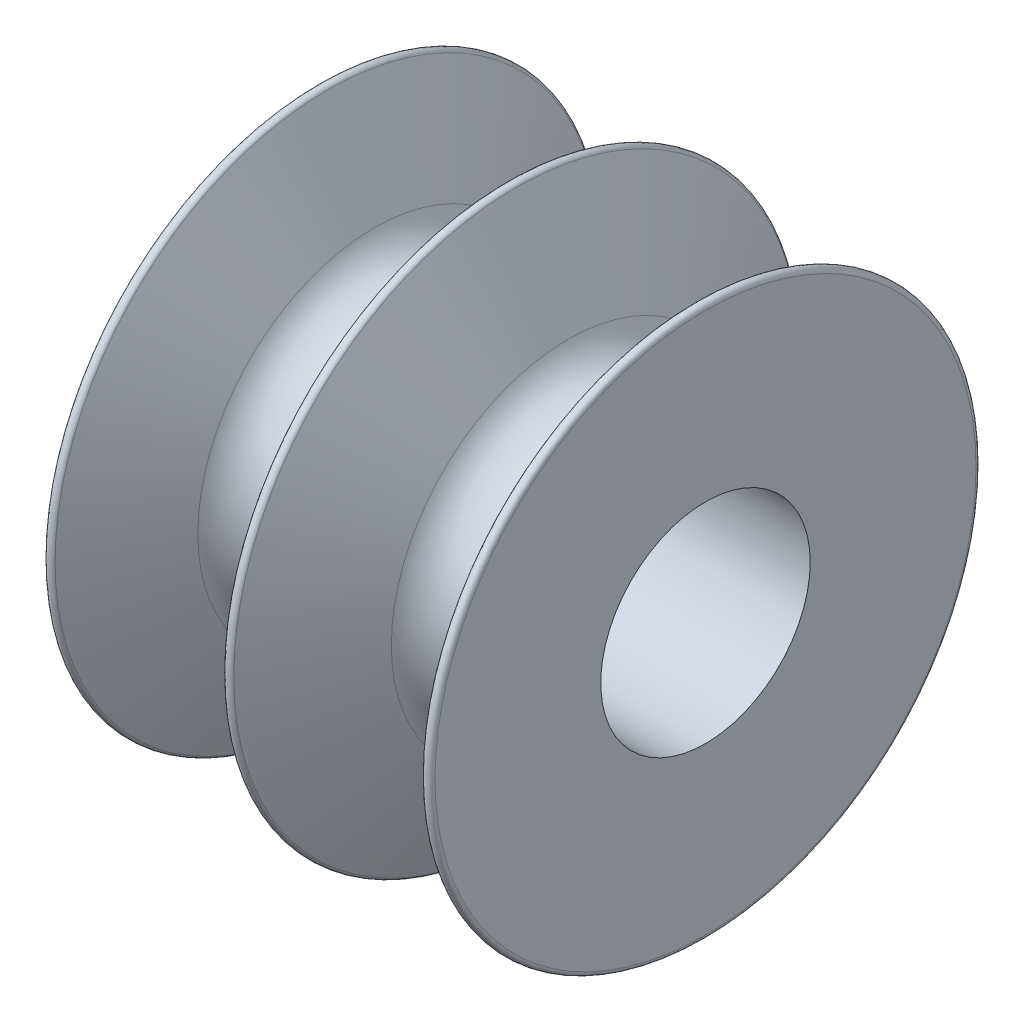
SolidWorks part; units mm, degrees
material "6061-T6 (SS)"
ref_plane "Front Plane" through (0, 0, 0) normal (0, 0, 1) x (1, 0, 0)
ref_plane "Top Plane" through (0, 0, 0) normal (0, 1, 0) x (1, 0, 0)
ref_plane "Right Plane" through (0, 0, 0) normal (1, 0, 0) x (0, 0, -1)
sketch "Sketch1" plane through (0, 0, 0) normal (0, 0, 1) x (1, 0, 0)
  line L0 (-602.9216, 0) -> (29543.159, 0) construction
  line L1 (-601.7144, 8.89) -> (29544.3662, 8.89) construction
  line L2 (0, 8.89) -> (0, -0.2516) construction
  line L3 (-1.905, 0) -> (-1.905, 6.35)
  line L7 (1.905, 0) -> (-1.905, 0)
  line L9 (1.905, 0) -> (1.905, 6.35)
  line L10 (-1.905, 6.35) -> (-1.0702, 4.6376)
  line L11 (1.905, 6.35) -> (1.0702, 4.6376)
  line L12 (1.905, 6.35) -> (2.54, 7.6526)
  line L13 (2.54, 7.6526) -> (2.54, 0)
  line L14 (-2.54, 7.6526) -> (-1.905, 6.35)
  line L15 (-2.54, 7.6526) -> (-2.54, 0)
  line L16 (-2.54, 0) -> (-1.905, 0)
  line L17 (1.905, 0) -> (2.54, 0)
  circle A1 centre (0, 5.1594) radius 1.1906 construction
  arc A3 (-1.0702, 4.6376) -> (1.0702, 4.6376) centre (0, 5.1594) ccw
  point P14 (0, 0)
  point P23 (0, 6.35)
  dimension "D3" = 2.3813
  dimension "D4" = 3.81
  dimension "D1" = 8.89
  dimension "D2" = 6.35
  dimension "D5" = 5.1594
  dimension "D6" = 0.635
  dimension "D7" = 0.635
revolve "Revolve1" add sketch "Sketch1" angle 360 about L0
sketch "Sketch4" plane through (2.54, 0, 0) normal (1, 0, 0) x (0, 0, -1)
  circle A0 centre (0, 0) radius 3.175
  dimension "D1" = 6.35
mirror "Mirror3" about plane through (2.54, 0, 0) normal (1, 0, 0) of "Revolve1"
fillet "Fillet2" radius 0.127 3 edges at (7.62, 0, 7.6526) (2.54, 0, 7.6526) (-2.54, 0, 7.6526)
sketch "Sketch5" plane through (7.62, 0, 0) normal (1, 0, 0) x (0, 0, -1)
  circle A0 centre (0, 0) radius 2.75
  dimension "D1" = 5.5
extrude "Cut-Extrude3" cut sketch "Sketch5" against normal through all
